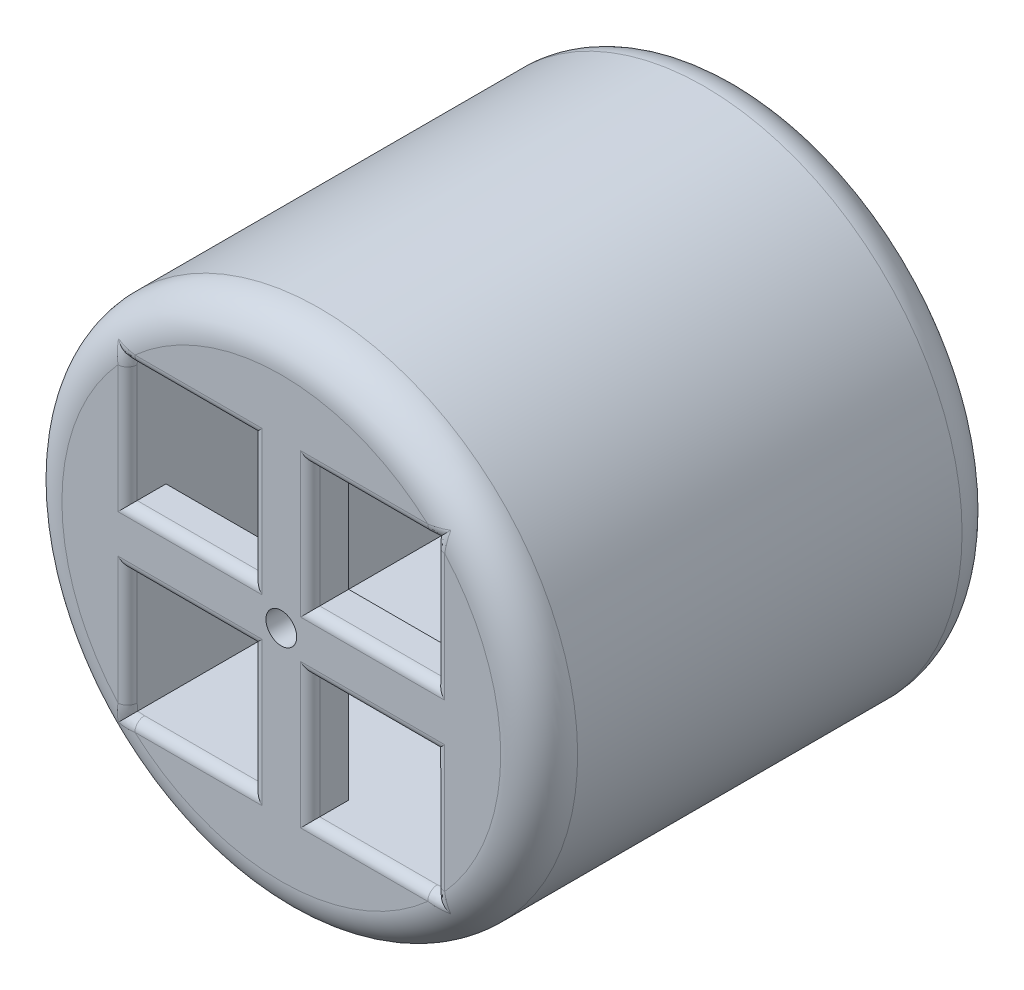
SolidWorks part; units mm, degrees
material "PET"
ref_plane "Front Plane" through (0, 0, 0) normal (0, 0, 1) x (1, 0, 0)
ref_plane "Top Plane" through (0, 0, 0) normal (0, 1, 0) x (1, 0, 0)
ref_plane "Right Plane" through (0, 0, 0) normal (1, 0, 0) x (0, 0, -1)
sketch "Sketch1" plane through (0, 0, 0) normal (0, 0, 1) x (1, 0, 0)
  line L0 (0, 0) -> (13.2613, 13.2613) construction
  line L1 (-12.7, -12.7) -> (12.7, -12.7) construction
  line L2 (-12.7, -12.7) -> (-12.7, 12.7) construction
  line L3 (-12.7, 12.7) -> (12.7, 12.7) construction
  line L4 (12.7, -12.7) -> (12.7, 12.7) construction
  line L5 (-12.7, -12.7) -> (12.7, 12.7) construction
  line L6 (-12.7, 12.7) -> (12.7, -12.7) construction
  circle A1 centre (0, 0) radius 18.7543
  circle A2 centre (0, 0) radius 21.2943
  point P0 (0, 0)
  point P9 (0, 0)
  dimension "D1" = 25.4
  dimension "D2" = 0.7937
  dimension "D3" = 2.54
extrude "Boss-Extrude1" add sketch "Sketch1" along normal blind 38.1
sketch "Sketch2" plane through (0, 0, 0) normal (0, 0, -1) x (-1, 0, 0)
  circle A1 centre (0, 0) radius 21.2943
  circle A2 centre (0, 0) radius 21.2943
  dimension "D1" = 0
extrude "Boss-Extrude2" add sketch "Sketch2" against normal blind 3.175
sketch "Sketch8" plane through (0, 0, 3.175) normal (0, 0, 1) x (1, 0, 0)
  line L1 (-12.7, -12.7) -> (12.7, -12.7)
  line L2 (-12.7, -12.7) -> (-12.7, 12.7)
  line L3 (-12.7, 12.7) -> (12.7, 12.7)
  line L4 (12.7, -12.7) -> (12.7, 12.7)
  line L5 (-12.7, -12.7) -> (12.7, 12.7) construction
  line L6 (-12.7, 12.7) -> (12.7, -12.7) construction
  circle A1 centre (0, 0) radius 18.7543
  circle A2 centre (0, 0) radius 18.7543
  point P0 (0, 0)
  dimension "D1" = 25.4
  dimension "D2" = 0
extrude "Boss-Extrude5" add sketch "Sketch8" along normal up to surface (34.925 mm away) up to face at (21.2943, 0, 38.1)
sketch "Sketch10" plane through (0, 0, 38.1) normal (0, 0, 1) x (1, 0, 0)
  line L0 (0, 0) -> (-12.7, 0) construction
  line L1 (-12.7, 12.7) -> (-12.7, -12.7) construction
  line L2 (-12.7, 2.3812) -> (-2.3812, 2.3812)
  line L3 (-2.3812, 2.3812) -> (-2.3813, 12.7)
  line L4 (12.7, 12.7) -> (-12.7, 12.7) construction
  line L5 (0, 0) -> (0, 12.7) construction
  line L6 (0, 8.8459) -> (-2.3813, 8.8459) construction
  line L7 (-6.35, 0) -> (-6.35, 2.3812) construction
  line L8 (-2.3813, -2.3812) -> (-2.3813, -12.7)
  line L9 (-12.7, -2.3812) -> (-2.3813, -2.3812)
  line L12 (-12.7, -12.7) -> (12.7, -12.7) construction
  line L13 (0, 10.4143) -> (2.3813, 10.4143) construction
  line L14 (-2.3813, -12.7) -> (2.3813, -12.7)
  line L15 (2.3813, 12.7) -> (-2.3813, 12.7)
  line L16 (-12.7, 2.3812) -> (-12.7, -2.3812)
  line L17 (2.3812, -2.3813) -> (2.3813, -12.7)
  line L18 (2.3813, 2.3812) -> (2.3813, 12.7)
  line L19 (12.7, 2.3812) -> (12.7, -2.3813)
  line L20 (12.7, 2.3812) -> (2.3813, 2.3812)
  line L21 (12.7, -2.3813) -> (2.3812, -2.3813)
  dimension "D1" = 2.3813
extrude "Boss-Extrude6" add sketch "Sketch10" against normal blind 3.175
fillet "Fillet6" radius 3.175 2 edges at (21.2943, 0, 0) (21.2943, 0, 38.1)
fillet "Fillet7" radius 0.7937 16 edges at (-2.3813, 7.5406, 38.1) (-7.5406, 12.7, 38.1) (-12.7, 7.5406, 38.1) (-7.5406, 2.3812, 38.1) (-7.5406, -12.7, 38.1) (-2.3813, -7.5406, 38.1) (-7.5406, -2.3812, 38.1) (-12.7, -7.5406, 38.1) (12.7, 7.5406, 38.1) (12.7, -7.5406, 38.1) (7.5406, 2.3812, 38.1) (7.5406, 12.7, 38.1) (2.3813, 7.5406, 38.1) (7.5406, -2.3813, 38.1) (2.3813, -7.5406, 38.1) (7.5406, -12.7, 38.1)
sketch "Sketch11" plane through (0, 0, 38.1) normal (0, 0, 1) x (1, 0, 0)
  circle A0 centre (0, 0) radius 1.27
  dimension "D1" = 2.54
extrude "Cut-Extrude3" cut sketch "Sketch11" against normal blind 6.731
